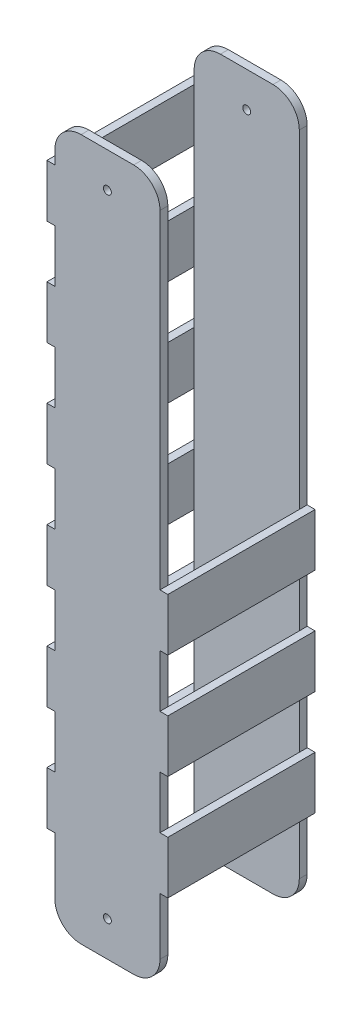
SolidWorks part; units mm, degrees
material "ENPH 253 Hardboard"
ref_plane "Front Plane" through (0, 0, 0) normal (0, 0, 1) x (1, 0, 0)
ref_plane "Top Plane" through (0, 0, 0) normal (0, 1, 0) x (1, 0, 0)
ref_plane "Right Plane" through (0, 0, 0) normal (1, 0, 0) x (0, 0, -1)
sketch "Sketch1" plane through (0, 0, 0) normal (0, 0, 1) x (1, 0, 0)
  line L1 (-10, 133.333) -> (10, 133.333)
  line L2 (-20, 123.333) -> (-20, -123.333)
  line L3 (-10, -133.333) -> (10, -133.333)
  line L4 (20, 123.333) -> (20, -123.333)
  line L5 (-20, 133.333) -> (20, -133.333) construction
  line L6 (-20, -133.333) -> (20, 133.333) construction
  arc A0 (10, -133.333) -> (20, -123.333) centre (10, -123.333) ccw
  arc A1 (-20, -123.333) -> (-10, -133.333) centre (-10, -123.333) ccw
  arc A2 (10, 133.333) -> (20, 123.333) centre (10, 123.333) cw
  arc A3 (-20, 123.333) -> (-10, 133.333) centre (-10, 123.333) cw
  point P0 (0, 0)
  dimension "D3" = 10
  dimension "D1" = 40
  dimension "D2" = 266.666
extrude "Boss-Extrude1" add sketch "Sketch1" along normal blind 3 from offset 50 contours L4 A0 L3 A1 L2 A3 L1 A2
extrude "Boss-Extrude2" add sketch "Sketch1<3>" against normal blind 3 separate body
sketch "Sketch1<3>" plane through (0, 0, 0) normal (0, 0, 1) x (1, 0, 0) same geometry as "Sketch1"
sketch "Sketch2" plane through (0, 0, 0) normal (0, 0, 1) x (1, 0, 0)
  line L0 (55, 0) -> (-55, 0) construction
  circle A0 centre (0, 119.9979) radius 1.5
  circle A1 centre (0, -119.9979) radius 1.5
  dimension "D2" = 3
extrude "Cut-Extrude1" cut sketch "Sketch2" against normal through all both and the other way through all
sketch "Sketch3" plane through (-20, 0, 0) normal (-1, 0, 0) x (0, 0, 1)
  line L0 (-3, 123.333) -> (-3, -123.333) construction
  line L1 (-3, 118.333) -> (53, 118.333)
  line L2 (-3, 118.333) -> (-3, 98.333)
  line L3 (-3, 98.333) -> (53, 98.333)
  line L4 (53, 118.333) -> (53, 98.333)
  line L5 (53, 123.333) -> (53, -123.333) construction
  line L6 (53, 133.333) -> (50, 133.333) construction
  line L7 (-3, 78.333) -> (-3, 58.333)
  line L8 (-3, 78.333) -> (53, 78.333)
  line L9 (53, 78.333) -> (53, 58.333)
  line L10 (-3, 58.333) -> (53, 58.333)
  line L11 (-3, 38.333) -> (-3, 18.333)
  line L12 (-3, 38.333) -> (53, 38.333)
  line L13 (53, 38.333) -> (53, 18.333)
  line L14 (-3, 18.333) -> (53, 18.333)
  line L15 (-3, -1.667) -> (-3, -21.667)
  line L16 (-3, -1.667) -> (53, -1.667)
  line L17 (53, -1.667) -> (53, -21.667)
  line L18 (-3, -21.667) -> (53, -21.667)
  line L19 (-3, -41.667) -> (-3, -61.667)
  line L20 (-3, -41.667) -> (53, -41.667)
  line L21 (53, -41.667) -> (53, -61.667)
  line L22 (-3, -61.667) -> (53, -61.667)
  line L23 (-3, -81.667) -> (-3, -101.667)
  line L24 (-3, -81.667) -> (53, -81.667)
  line L25 (53, -81.667) -> (53, -101.667)
  line L26 (-3, -101.667) -> (53, -101.667)
  dimension "D1" = 20
  dimension "D2" = 15
  dimension "D3" = 6
extrude "Boss-Extrude4" add sketch "Sketch3" along normal blind 3
sketch "Sketch4" plane through (20, 0, 0) normal (1, 0, 0) x (0, 0, -1)
  line L0 (-53, -41.667) -> (-53, -61.667)
  line L1 (-53, -1.667) -> (3, -1.667)
  line L2 (-53, -1.667) -> (-53, -21.667)
  line L3 (-53, -21.667) -> (3, -21.667)
  line L4 (3, -1.667) -> (3, -21.667)
  line L5 (-53, -41.667) -> (3, -41.667)
  line L6 (3, -41.667) -> (3, -61.667)
  line L7 (-53, -61.667) -> (3, -61.667)
  line L8 (-53, -81.667) -> (-53, -101.667)
  line L9 (-53, -81.667) -> (3, -81.667)
  line L10 (3, -81.667) -> (3, -101.667)
  line L11 (-53, -101.667) -> (3, -101.667)
  dimension "D1" = 3
extrude "Boss-Extrude5" add sketch "Sketch4" along normal blind 3
